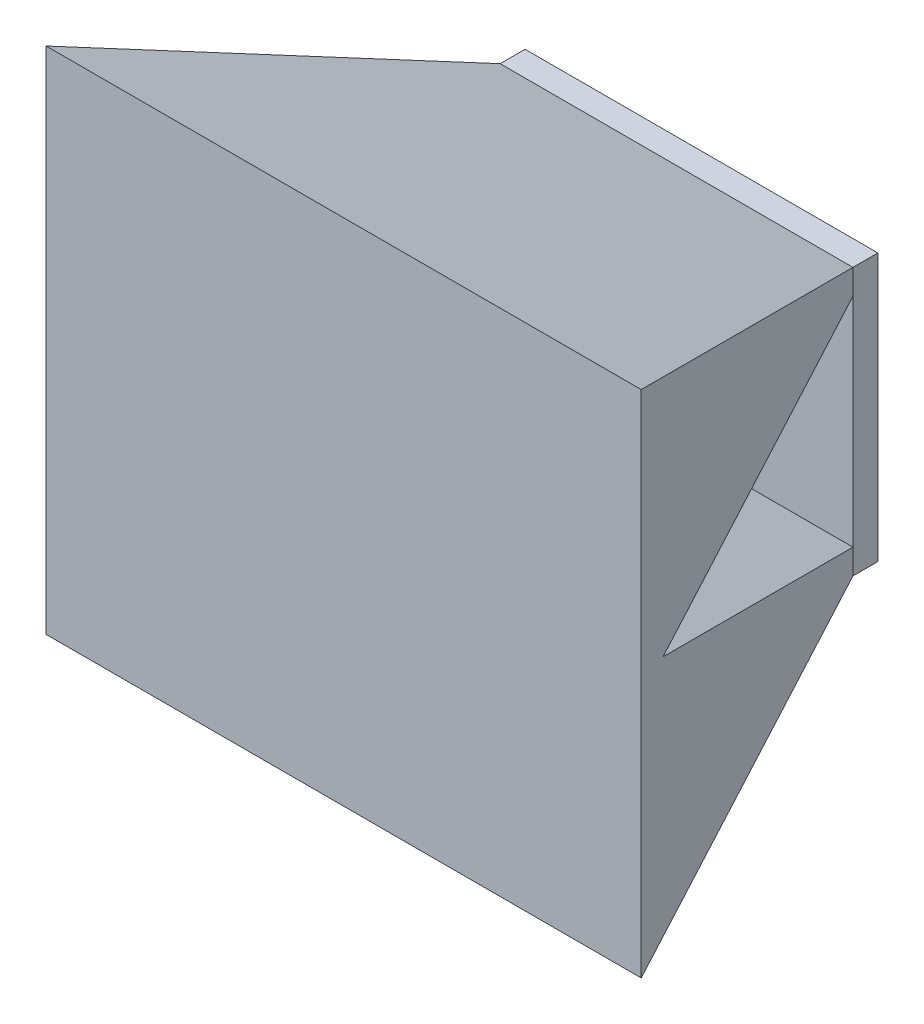
SolidWorks part; units mm, degrees
ref_plane "Front Plane" through (0, 0, 0) normal (0, 0, 1) x (1, 0, 0)
ref_plane "Top Plane" through (0, 0, 0) normal (0, 1, 0) x (1, 0, 0)
ref_plane "Right Plane" through (0, 0, 0) normal (1, 0, 0) x (0, 0, -1)
sketch "Sketch1" plane through (0, 0, 0) normal (0, 0, 1) x (1, 0, 0)
  line L1 (-21.2, -16.06) -> (21.2, -16.06)
  line L2 (-21.2, -16.06) -> (-21.2, 16.06)
  line L3 (-21.2, 16.06) -> (21.2, 16.06)
  line L4 (21.2, -16.06) -> (21.2, 16.06)
  line L5 (-21.2, -16.06) -> (21.2, 16.06) construction
  line L6 (-21.2, 16.06) -> (21.2, -16.06) construction
  point P0 (0, 0)
  dimension "D1" = 32.12
  dimension "D2" = 42.4
extrude "Boss-Extrude1" add sketch "Sketch1" along normal blind 3
sketch "Sketch2" plane through (0, 0, 3) normal (0, 0, 1) x (1, 0, 0)
  line L0 (21.2, -16.06) -> (21.2, 16.06) construction
  line L1 (-21.2, 16.06) -> (21.2, 16.06)
  line L2 (-21.2, 16.06) -> (-21.2, 13.06)
  line L3 (-21.2, 13.06) -> (21.2, 13.06)
  line L4 (21.2, 16.06) -> (21.2, 13.06)
  line L6 (-21.2, -16.06) -> (21.2, -16.06)
  line L7 (-21.2, -16.06) -> (-21.2, -13.06)
  line L8 (-21.2, -13.06) -> (21.2, -13.06)
  line L9 (21.2, -16.06) -> (21.2, -13.06)
  line L10 (-1.5, -16.06) -> (1.5, -16.06)
  line L11 (-1.5, -16.06) -> (-1.5, 16.06)
  line L12 (-1.5, 16.06) -> (1.5, 16.06)
  line L13 (1.5, -16.06) -> (1.5, 16.06)
  line L14 (-1.5, -16.06) -> (1.5, 16.06) construction
  line L15 (-1.5, 16.06) -> (1.5, -16.06) construction
  point P11 (0, 0)
  line M4 (21.2, -16.06) -> (21.2, 16.06)
  line M5 (21.2, 16.06) -> (-21.2, 16.06)
  line M6 (-21.2, 16.06) -> (-21.2, -16.06)
  dimension "D1" = 3
  dimension "D2" = 3
  dimension "D3" = 3
extrude "Boss-Extrude2" add sketch "Sketch2" along normal blind 40 draft 20 contours L8 L13 L3 L11 | L3 L11 L1 M6 | L13 L3 M4 M5 | L3 L13 L1 L11
